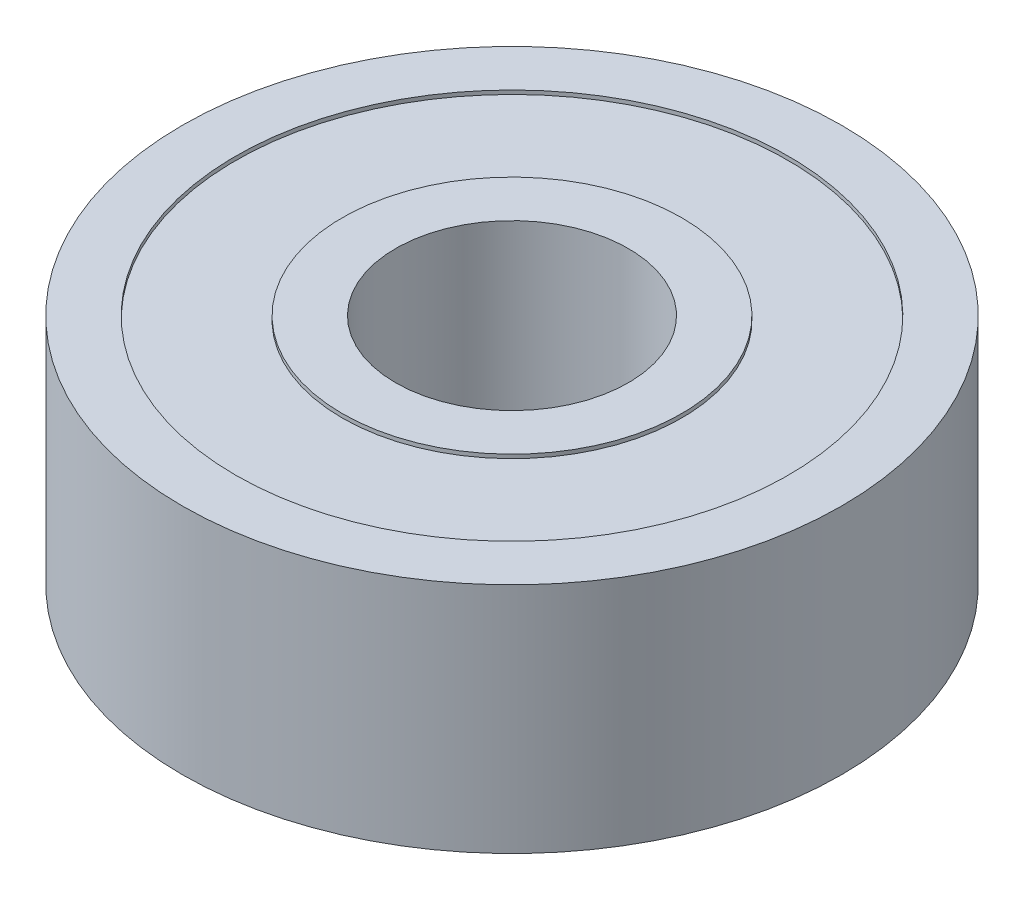
SolidWorks part; units mm, degrees
ref_plane "Front plane" through (0, 0, 0) normal (0, 0, 1) x (1, 0, 0)
ref_plane "Top plane" through (0, 0, 0) normal (0, 1, 0) x (1, 0, 0)
ref_plane "Right plane" through (0, 0, 0) normal (1, 0, 0) x (0, 0, -1)
ref_axis "Axis X" through (0, 0, 0) along (1, 0, 0)
ref_axis "Axis Y" through (0, 0, 0) along (0, 1, 0)
ref_axis "Axis Z" through (0, 0, 0) along (0, 0, 1)
sketch "Sketch1" plane through (0, 0, 0) normal (0, 1, 0) x (1, 0, 0)
  circle A0 centre (0, 0) radius 8.5
  circle A1 centre (0, 0) radius 3
  dimension "D1" = 17
  dimension "D2" = 6
extrude "Extrude1" add sketch "Sketch1" along normal blind 6
sketch "Sketch2" plane through (0, 6, 0) normal (0, 1, 0) x (1, 0, 0)
  circle A2 centre (0, 0) radius 7.125
  circle A3 centre (0, 0) radius 7.125
  circle A5 centre (0, 0) radius 4.375
  circle A6 centre (0, 0) radius 4.375
  dimension "D1" = 1.375
  dimension "D2" = 1.375
extrude "Extrude2" cut sketch "Sketch2" against normal blind 0.1
sketch "Sketch3" plane through (0, 0, 0) normal (0, -1, 0) x (1, 0, 0)
  circle A2 centre (0, 0) radius 7.125
  circle A3 centre (0, 0) radius 7.125
  circle A5 centre (0, 0) radius 4.375
  circle A6 centre (0, 0) radius 4.375
  dimension "D1" = 1.375
  dimension "D2" = 1.375
extrude "Extrude3" cut sketch "Sketch3" against normal blind 0.1
equation "\"motor_D\"= 49'Motor diameter"
equation "\"motor_H\"= 19'Motor heigh"
equation "\"motor_d1\"= 38.5'Seating diameter of screws on the fixed part of the motor"
equation "\"motor_s1\"= 2.5'Screws diameter on the fixed part of motor"
equation "\"motor_a2\"= 0'Seating parameter in rectangle of screws on the moving part of the motor"
equation "\"motor_s2\"= 3'Screws diameter on the moving part of motor"
equation "\"motor_Dc\"= 5'Central hole diameter of motor"
equation "\"bearing_d1\"= 6'Bearing inner diameter"
equation "\"bearing_d2\"= 17'Bearing external diameter"
equation "\"bearing h\"= 6'Bearing heigh"
equation "\"pin_d\"= 2'Pin diameter"
equation "\"pin_h\"= 13'Pin heigh"
equation "\"magnet_d1\"= 5'Magnet inner diameter"
equation "\"magnet_d2\"= 9.5'Magnet external diameter"
equation "\"magnet_h\"= 3'Magnet heigh"
equation "\"motor_b2\"= 0'Seating parameter in rectangle of screws on the moving part of the motor"
equation "\"motor_d2\"= 25'Seating diameter of screws on the moving part of the motor (if this parameter is not determine, write 0)"
equation "\"motor_cmd\"= 17'Central magnet mount diameter"
equation "\"motor_cmh\"= 1'Central magnet mount heigh (if not write 0)"
equation "\"motor_whR\"= 17'Distance from center of motor to wires"
equation "\"D1@Sketch1\"=\"bearing_d2\""
equation "\"D2@Sketch1\"=\"bearing_d1\""
equation "\"D1@Extrude1\"=\"bearing h\""
equation "\"D1@Sketch2\"=(\"bearing_d2\"-\"bearing_d1\")/2/4"
equation "\"D2@Sketch2\"=\"D1@Sketch2\""
equation "\"D1@Extrude2\"=0.1"
equation "\"D2@Sketch3\"=(\"bearing_d2\"-\"bearing_d1\")/2/4"
equation "\"D1@Sketch3\"=\"D2@Sketch3\""
equation "\"print_offset\"= 0.2'Offset for printing holes"
equation "\"ft_sensor_d1\"= 9.8"
equation "\"ft_sensor_d2\"= 24.9"
equation "\"ft_sensor_d3\"= 22.6'Inner diameter of "
equation "\"ft_sensor_h\"= 7.1"
equation "\"ft_sensor_whD\" = 5"
